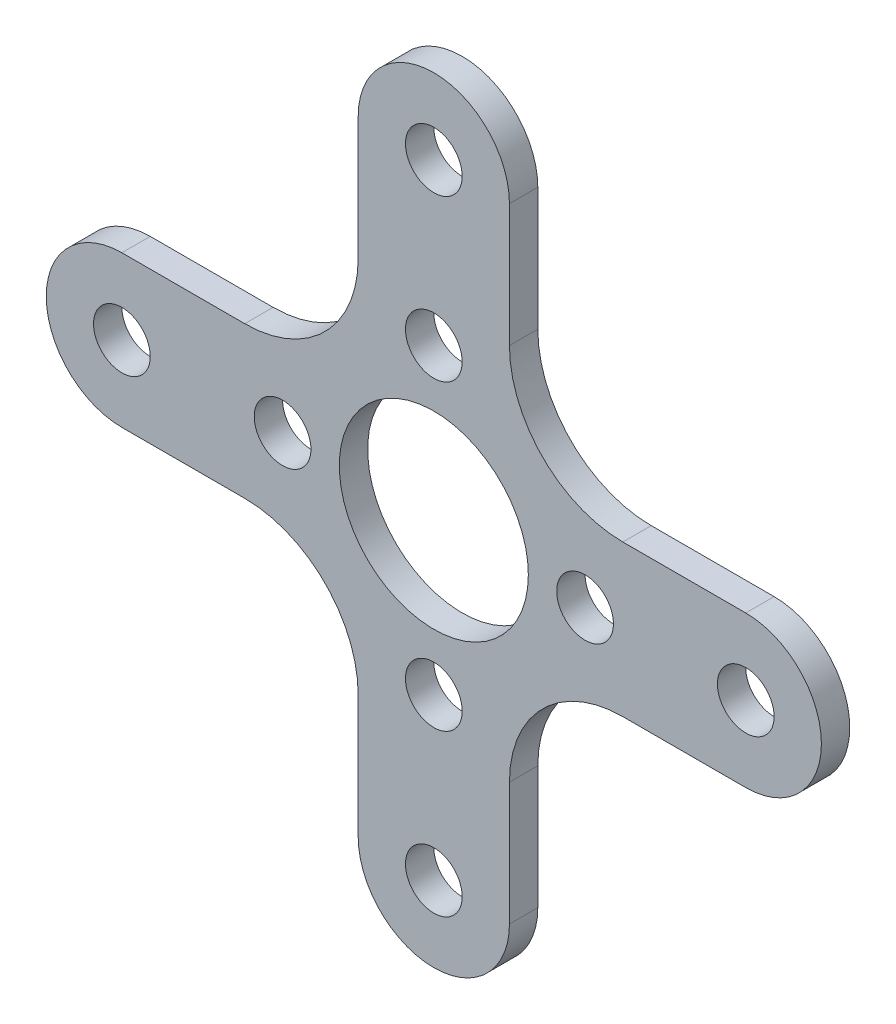
SolidWorks part; units mm, degrees
ref_plane "Ön Düzlem" through (0, 0, 0) normal (0, 0, 1) x (1, 0, 0)
ref_plane "Üst Düzlem" through (0, 0, 0) normal (0, 1, 0) x (1, 0, 0)
ref_plane "Sağ Düzlem" through (0, 0, 0) normal (1, 0, 0) x (0, 0, -1)
sketch "Çizim1" plane through (0, 0, 0) normal (0, 0, 1) x (1, 0, 0)
  line L0 (0, 0) -> (0, 16.5) construction
  line L1 (10, 4) -> (16.5, 4)
  line L2 (10, -4) -> (16.5, -4)
  line L3 (4, -10) -> (4, -16.5)
  line L4 (-4, -10) -> (-4, -16.5)
  line L5 (-10, -4) -> (-16.5, -4)
  line L6 (-10, 4) -> (-16.5, 4)
  line L7 (-4, 10) -> (-4, 16.5)
  line L9 (4, 10) -> (4, 16.5)
  circle A0 centre (0, 8) radius 1.5
  arc A1 (4, 16.5) -> (-4, 16.5) centre (0, 16.5) ccw
  arc A2 (16.5, -4) -> (16.5, 4) centre (16.5, 0) ccw
  circle A3 centre (16.5, 0) radius 1.5
  circle A4 centre (8, 0) radius 1.5
  arc A5 (10, -4) -> (4, -10) centre (10, -10) ccw
  arc A6 (4, 10) -> (10, 4) centre (10, 10) ccw
  arc A7 (-4, -16.5) -> (4, -16.5) centre (0, -16.5) ccw
  circle A8 centre (0, 16.5) radius 1.5
  circle A9 centre (0, -16.5) radius 1.5
  circle A10 centre (0, -8) radius 1.5
  arc A11 (-4, -10) -> (-10, -4) centre (-10, -10) ccw
  circle A12 centre (0, 0) radius 5
  arc A13 (-16.5, 4) -> (-16.5, -4) centre (-16.5, 0) ccw
  circle A14 centre (-16.5, 0) radius 1.5
  circle A15 centre (-8, 0) radius 1.5
  arc A16 (-10, 4) -> (-4, 10) centre (-10, 10) ccw
  point P2 (0, 0)
  point P9 (0, 0)
  point P39 (0, 0)
  point P49 (0, 0)
  dimension "D3" = 4
  dimension "D4" = 10
  dimension "D5" = 10
  dimension "D6" = 3
  dimension "D1" = 6
  dimension "D2" = 16.5
  dimension "D7" = 4
  dimension "D8" = 8
  dimension "D9" = 4
extrude "Yükseklik-Ekstrüzyon1" add sketch "Çizim1" along normal blind 1.5
